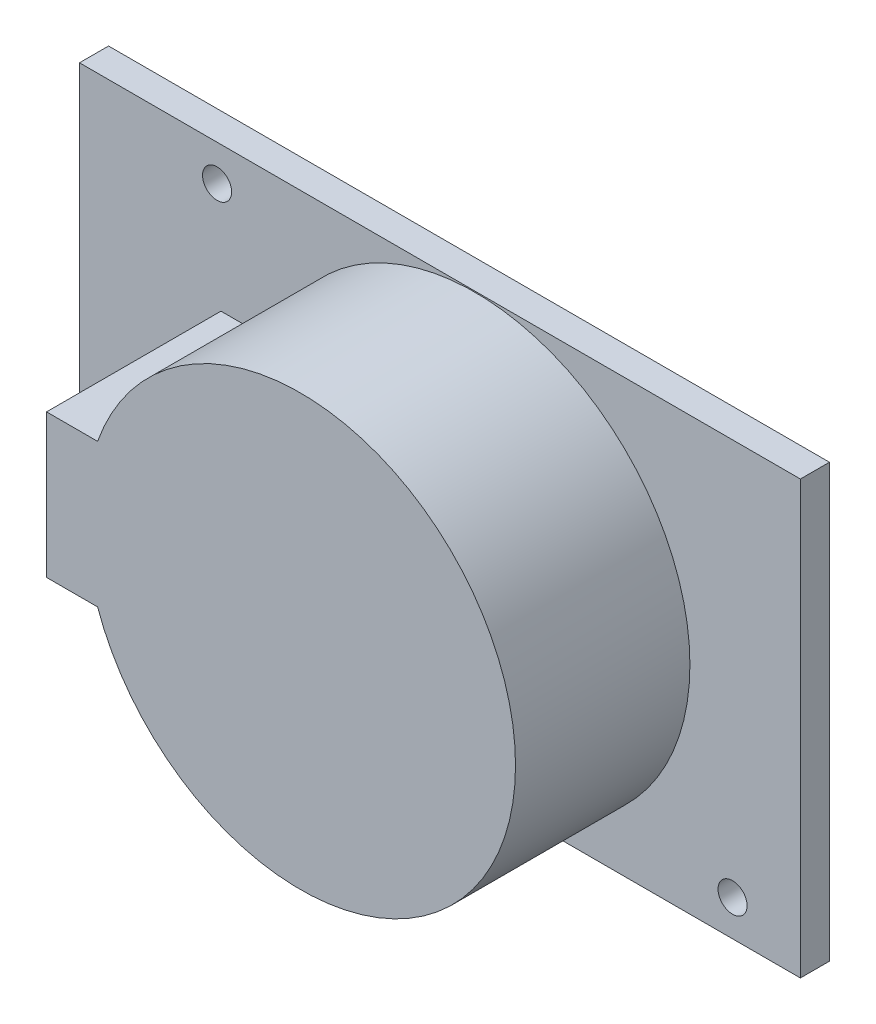
SolidWorks part; units mm, degrees
ref_plane "前基準面" through (0, 0, 0) normal (0, 0, 1) x (1, 0, 0)
ref_plane "上基準面" through (0, 0, 0) normal (0, 1, 0) x (1, 0, 0)
ref_plane "右基準面" through (0, 0, 0) normal (1, 0, 0) x (0, 0, -1)
sketch "草圖1" plane through (0, 0, 0) normal (0, 0, 1) x (1, 0, 0)
  line L0 (102.3393, 5.4435) -> (102.3393, 17.8435) construction
  line L1 (45.1393, 29.0435) -> (82.3393, 29.0435)
  line L2 (45.1393, 29.0435) -> (45.1393, 6.7435)
  line L3 (45.1393, 6.7435) -> (82.3393, 6.7435)
  line L4 (82.3393, 29.0435) -> (82.3393, 6.7435)
  line L5 (13.7314, 4.7435) -> (101.6393, 4.7435) construction
  circle A0 centre (78.8393, 8.5935) radius 0.75
  circle A1 centre (52.2393, 27.1935) radius 0.75
  circle A3 centre (52.2393, 8.5935) radius 0.75
  dimension "D5" = 1.5
  dimension "D6" = 3.5
  dimension "D7" = 1.85
  dimension "D8" = 7.1
  dimension "D9" = 1.85
  dimension "D1" = 37.2
  dimension "D2" = 22.3
  dimension "D3" = 20
  dimension "D4" = 2
extrude "填料-伸長1" add sketch "草圖1" along normal blind 5
sketch "草圖3" plane through (0, 0, 5) normal (0, 0, 1) x (1, 0, 0)
  line L0 (82.3393, 29.0435) -> (45.1393, 29.0435) construction
  line L1 (45.1393, 6.7435) -> (82.3393, 6.7435) construction
  line L2 (45.1393, 29.0435) -> (45.1393, 6.7435) construction
  line L6 (52.4393, 14.1935) -> (55.0741, 14.1935)
  line L7 (52.4393, 14.1935) -> (52.4393, 21.5935)
  line L8 (52.4393, 21.5935) -> (55.0741, 21.5935)
  arc A0 (55.0741, 14.1935) -> (55.0741, 21.5935) centre (65.5393, 17.8935) ccw
  point P12 (54.4393, 17.8935)
  dimension "D1" = 22.2
  dimension "D3" = 11.15
  dimension "D4" = 20.4
  dimension "D2" = 11.15
extrude "除料-伸長2" cut sketch "草圖1<3>" along normal blind 3.5
sketch "草圖1<3>" plane through (0, 0, 0) normal (0, 0, 1) x (1, 0, 0) same geometry as "草圖1"
extrude "填料-伸長3" add sketch "草圖3" along normal blind 9
sketch "草圖4" plane through (0, 0, 3.5) normal (0, 0, -1) x (-1, 0, 0)
  line L0 (-45.1393, 6.7435) -> (-82.3393, 6.7435) construction
  line L1 (-71.8393, 17.7435) -> (-61.4393, 17.7435)
  line L2 (-71.8393, 17.7435) -> (-71.8393, 10.2435)
  line L3 (-71.8393, 10.2435) -> (-61.4393, 10.2435)
  line L4 (-61.4393, 17.7435) -> (-61.4393, 10.2435)
  line L5 (-82.3393, 6.7435) -> (-82.3393, 29.0435) construction
  dimension "D1" = 10.4
  dimension "D2" = 7.5
  dimension "D3" = 3.5
  dimension "D4" = 10.5
extrude "填料-伸長4" add sketch "草圖4" along normal blind 3.5
